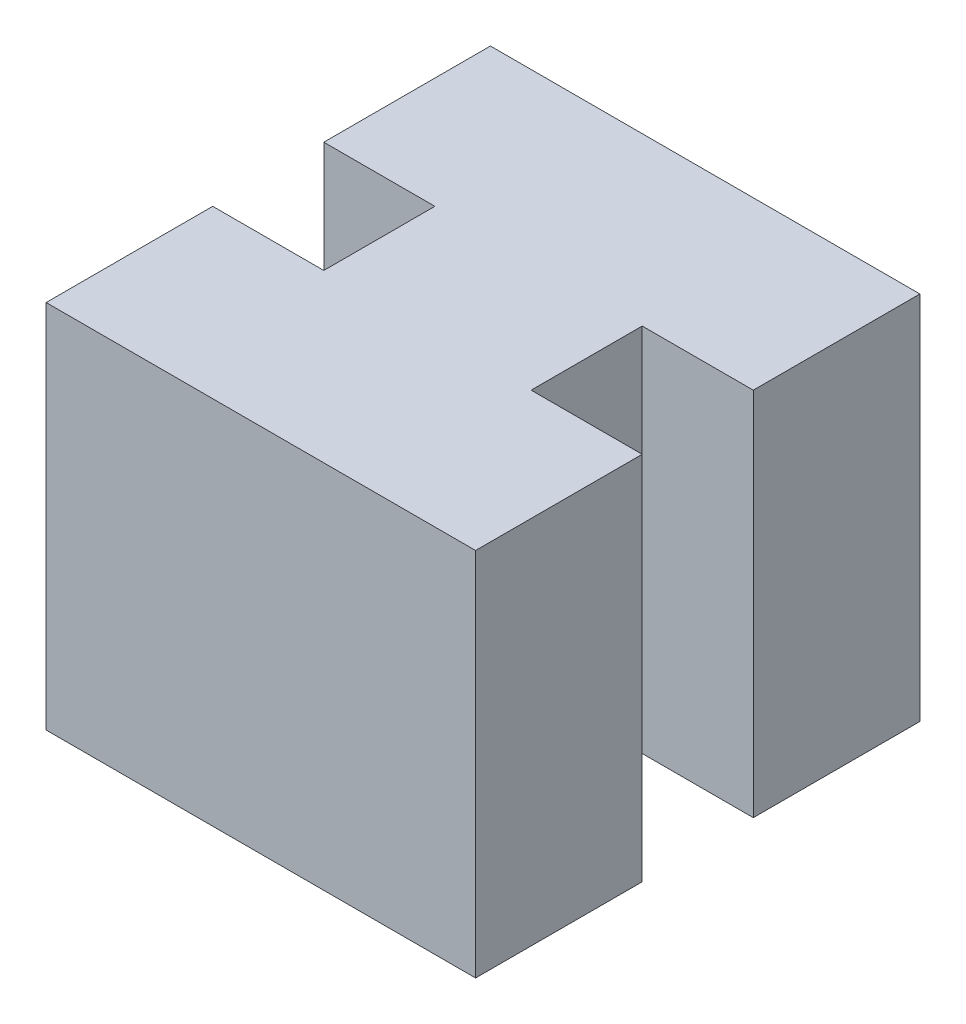
SolidWorks part; units mm, degrees
material "ABS"
ref_plane "Front" through (0, 0, 0) normal (0, 0, 1) x (1, 0, 0)
ref_plane "Top" through (0, 0, 0) normal (0, 1, 0) x (1, 0, 0)
ref_plane "Right" through (0, 0, 0) normal (1, 0, 0) x (0, 0, -1)
sketch "Sketch1" plane through (0, 0, 0) normal (0, 1, 0) x (1, 0, 0)
  line L1 (-2.9, 3) -> (2.9, 3)
  line L2 (-2.9, 3) -> (-2.9, -3)
  line L3 (-2.9, -3) -> (2.9, -3)
  line L4 (2.9, 3) -> (2.9, -3)
  line L5 (-2.9, 3) -> (2.9, -3) construction
  line L6 (-2.9, -3) -> (2.9, 3) construction
  line L7 (-2.9, 0.75) -> (-1.4, 0.75)
  line L8 (-2.9, 0.75) -> (-2.9, -0.75)
  line L9 (-2.9, -0.75) -> (-1.4, -0.75)
  line L10 (-1.4, 0.75) -> (-1.4, -0.75)
  line L11 (-2.9, 0.75) -> (-1.4, -0.75) construction
  line L12 (-2.9, -0.75) -> (-1.4, 0.75) construction
  line L13 (1.4, 0.75) -> (2.9, 0.75)
  line L14 (1.4, 0.75) -> (1.4, -0.75)
  line L15 (1.4, -0.75) -> (2.9, -0.75)
  line L16 (2.9, 0.75) -> (2.9, -0.75)
  line L17 (1.4, 0.75) -> (2.9, -0.75) construction
  line L18 (1.4, -0.75) -> (2.9, 0.75) construction
  point P0 (0, 0)
  point P5 (2.15, 0)
  point P6 (-2.15, 0)
  dimension "D1" = 5.8
  dimension "D2" = 6
  dimension "D3" = 1.5
extrude "Boss-Extrude1" add sketch "Sketch1" along normal mid plane 5 contours L15 L14 L13 L4 L1 L2 L7 L10 L9 L3 region at (0, 0, 0)
